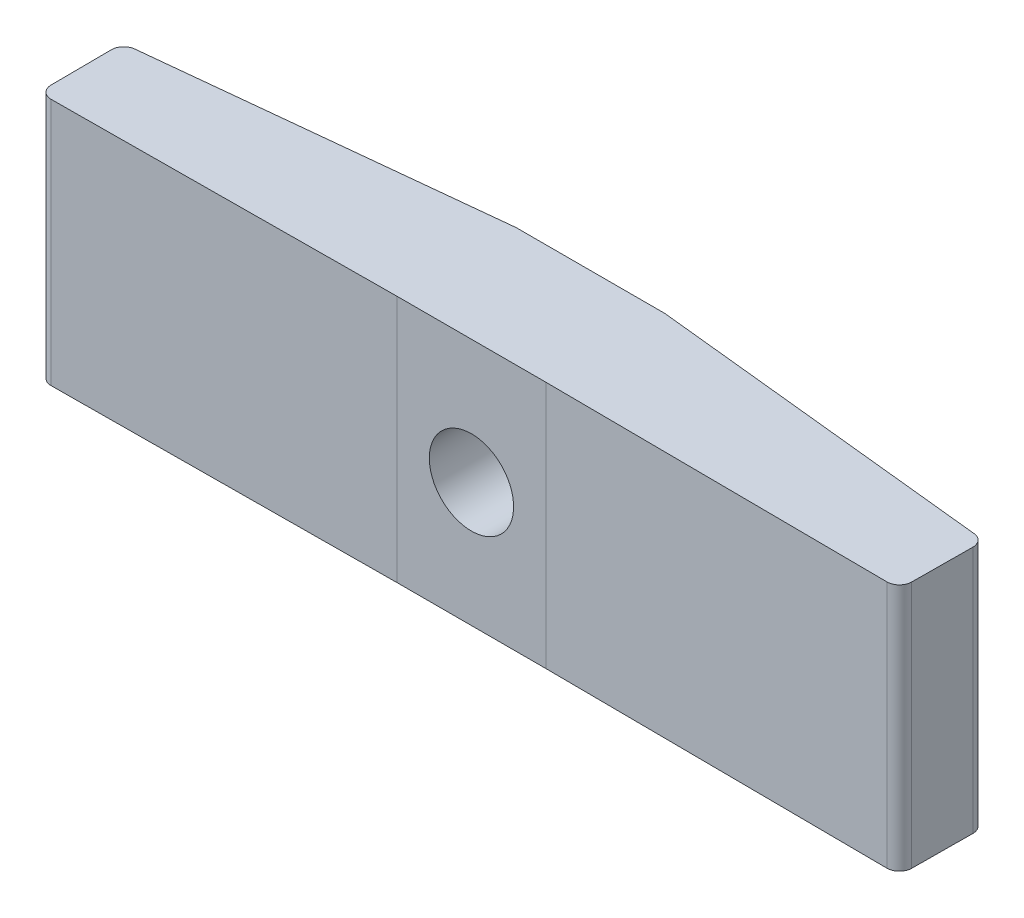
SolidWorks part; units mm, degrees
ref_plane "Front" through (0, 0, 0) normal (0, 0, 1) x (1, 0, 0)
ref_plane "Top" through (0, 0, 0) normal (0, 1, 0) x (1, 0, 0)
ref_plane "Right" through (0, 0, 0) normal (1, 0, 0) x (0, 0, -1)
sketch "Sketch1" plane through (0, 0, 0) normal (0, 1, 0) x (1, 0, 0)
  line L0 (0, 0) -> (34.7, 0) construction
  line L1 (17.35, 0) -> (17.35, 17.8266) construction
  line L2 (20.35, 0.1) -> (14.35, 0.1)
  line L3 (14.35, 0.1) -> (0, 0)
  line L4 (0, 0) -> (-0.0237, 3.4)
  line L9 (20.35, 4.9) -> (34.7237, 3.4)
  line L10 (20.35, 4.9) -> (14.35, 4.9)
  line L11 (14.35, 4.9) -> (-0.0237, 3.4)
  line L14 (34.7, 0) -> (34.7237, 3.4)
  line L15 (20.35, 0.1) -> (34.7, 0)
  line L16 (14.35, 4.9) -> (14.35, 0.1) construction
  point P5 (17.35, 14.222)
  point P25 (17.35, 4.9)
  point P26 (17.35, 3.4)
  point P28 (17.35, 14.222)
  point P29 (17.35, 0.1)
  dimension "D1" = 34.7
  dimension "D2" = 0.2
  dimension "D3" = 4.8
  dimension "D4" = 1.5
  dimension "D6" = 6
  dimension "D8" = 3.4
extrude "Boss-Extrude1" add sketch "Sketch1" along normal blind 10
fillet "Fillet1" [suppressed] radius 0.1
fillet "Fillet2" radius 0.5 4 edges at (-0.0237, 5, -3.4) (34.7237, 5, -3.4) (34.7, 5, 0) (0, 5, 0)
sketch "Sketch2" plane through (0, 0, -4.9) normal (0, 0, -1) x (-1, 0, 0)
  line L0 (-17.35, 5) -> (-17.35, 0) construction
  line L1 (-20.35, 0) -> (-14.35, 0) construction
  line L2 (-17.35, 5) -> (-17.35, 10) construction
  line L3 (-20.35, 10) -> (-14.35, 10) construction
  circle A0 centre (-17.35, 5) radius 1.7
  dimension "D1" = 3.4
extrude "Cut-Extrude1" cut sketch "Sketch2" against normal through all
sketch "Sketch3" plane through (0.7251, 0, -6.948) normal (0.1038, 0, -0.9946) x (-0.9946, 0, -0.1038)
  line L0 (-33.7295, 1) -> (-19.7315, 1) construction
  line L1 (-33.7295, 10) -> (-33.7295, 0) construction
  line L2 (-19.7315, 10) -> (-19.7315, 0) construction
  line L4 (-33.7295, 0) -> (-19.7315, 0) construction
  text T0 "BCL" font "Century Gothic" height in points 20
  dimension "D1" = 1
extrude "Boss-Extrude2" [suppressed] add sketch "Sketch3" along normal blind 0.4
sketch "Sketch4" plane through (-0.3512, 0, -3.3658) normal (-0.1038, 0, -0.9946) x (-0.9946, 0, 0.1038)
  line L0 (-14.7811, 1) -> (-0.783, 1) construction
  line L1 (-14.7811, 10) -> (-14.7811, 0) construction
  line L2 (-0.783, 0) -> (-0.783, 10) construction
  line L3 (-14.7811, 0) -> (-0.783, 0) construction
  text T0 "02" font "Century Gothic" height in points 20
  dimension "D1" = 1
extrude "Boss-Extrude3" [suppressed] add sketch "Sketch4" along normal blind 0.4
sketch "Sketch5" plane through (-0.3512, 0, -3.3658) normal (-0.1038, 0, -0.9946) x (-0.9946, 0, 0.1038)
  line L0 (-14.7811, 1) -> (-0.783, 1) construction
  line L1 (-14.7811, 10) -> (-14.7811, 0) construction
  line L2 (-0.783, 0) -> (-0.783, 10) construction
  line L3 (-14.7811, 0) -> (-0.783, 0) construction
  text T0 "...."
  dimension "D1" = 1
extrude "revision indication" add sketch "Sketch5" along normal blind 0.4
